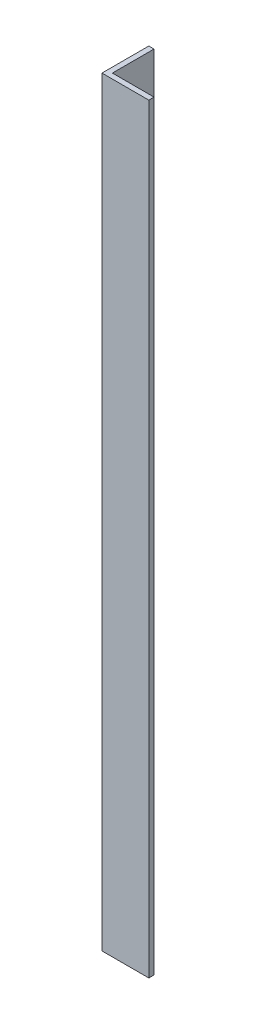
SolidWorks part; units mm, degrees
ref_plane "Спереди" through (0, 0, 0) normal (0, 0, 1) x (1, 0, 0)
ref_plane "Сверху" through (0, 0, 0) normal (0, 1, 0) x (1, 0, 0)
ref_plane "Справа" through (0, 0, 0) normal (1, 0, 0) x (0, 0, -1)
sketch "Эскиз1" plane through (0, 0, 0) normal (0, 1, 0) x (1, 0, 0)
  line L0 (0, 45) -> (0, 0)
  line L1 (0, 0) -> (45, 0)
extrude "Вытянуть-Тонкостенный1" add sketch "Эскиз1" along normal blind 730 thin thin type one direction reverse wall 5
